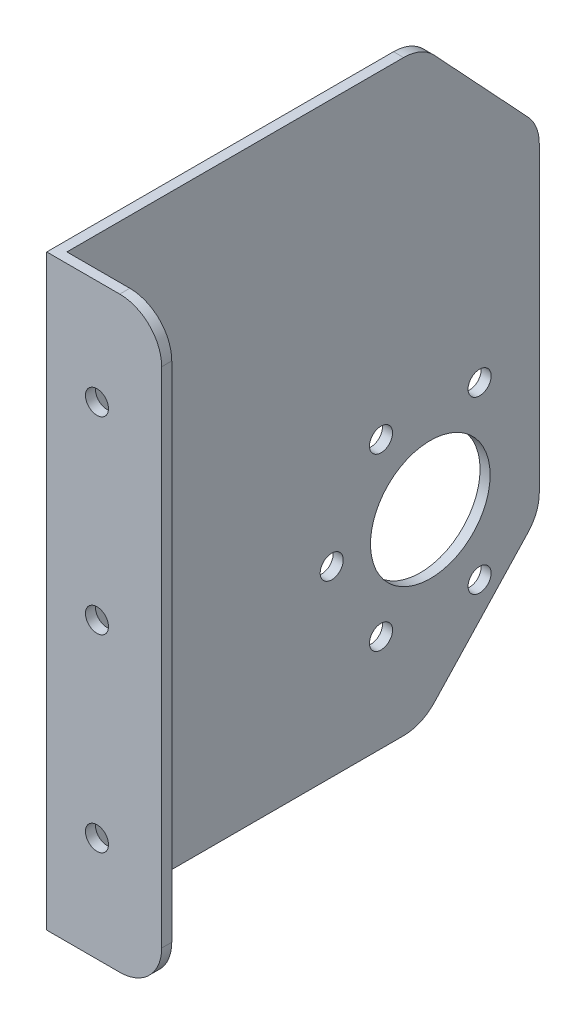
SolidWorks part; units mm, degrees
ref_plane "Front Plane" through (0, 0, 0) normal (0, 0, 1) x (1, 0, 0)
ref_plane "Top Plane" through (0, 0, 0) normal (0, 1, 0) x (1, 0, 0)
ref_plane "Right Plane" through (0, 0, 0) normal (1, 0, 0) x (0, 0, -1)
sketch "Sketch1" plane through (0, 0, 0) normal (1, 0, 0) x (0, 0, -1)
  line L1 (0, 0) -> (115, 0)
  line L2 (0, 0) -> (0, -140)
  line L3 (0, -140) -> (115, -140)
  line L4 (115, 0) -> (115, -140)
  dimension "D1" = 115
  dimension "D2" = 140
extrude "Boss-Extrude1" add sketch "Sketch1" along normal blind 2.4
sketch "Sketch2" plane through (2.4, 0, 0) normal (1, 0, 0) x (0, 0, -1)
  line L0 (87, 0) -> (115, -30)
  line L1 (115, 0) -> (0, 0) construction
  line L2 (115, -140) -> (115, 0) construction
  line L3 (115, -30) -> (142.6162, -32.5054)
  line L4 (142.6162, -32.5054) -> (142.6162, 14.8756)
  line L5 (142.6162, 14.8756) -> (87, 0)
  line L6 (115, -110) -> (87, -140)
  line L7 (0, -140) -> (115, -140) construction
  line L8 (87, -140) -> (87, -152.6611)
  line L9 (87, -152.6611) -> (136.31, -152.6611)
  line L10 (136.31, -152.6611) -> (115, -110)
  line L12 (0, 0) -> (0, -140) construction
  dimension "D1" = 30
  dimension "D2" = 87
  dimension "D3" = 87
  dimension "D4" = 30
extrude "Cut-Extrude1" cut sketch "Sketch2" against normal through all
fillet "Fillet1" radius 10 4 edges at (1.2, -140, -87) (1.2, -110, -115) (1.2, -30, -115) (1.2, 0, -87)
sketch "Sketch3" plane through (2.4, 0, 0) normal (1, 0, 0) x (0, 0, -1)
  line L0 (82.6545, 0) -> (0, 0) construction
  line L1 (0, -140) -> (2.4, -140)
  line L2 (0, -140) -> (0, 0)
  line L3 (0, 0) -> (2.4, 0)
  line L4 (2.4, -140) -> (2.4, 0)
  dimension "D1" = 2.4
extrude "Boss-Extrude2" add sketch "Sketch3" along normal blind 25
fillet "Fillet2" radius 10 2 edges at (27.4, -140, -1.2) (27.4, 0, -1.2)
sketch "Sketch4" plane through (0, 0, 0) normal (0, 0, 1) x (1, 0, 0)
  line L0 (17.4, 0) -> (0, 0) construction
  line L1 (17.4, -140) -> (0, -140) construction
  line L2 (27.4, -10) -> (27.4, -130) construction
  circle A0 centre (11.975, -70) radius 2.75
  circle A1 centre (11.975, -25) radius 2.75
  circle A2 centre (11.975, -115) radius 2.75
  point P12 (27.4, -70)
  dimension "D1" = 5.5
  dimension "D2" = 5.5
  dimension "D3" = 5.5
  dimension "D4" = 25
  dimension "D5" = 25
extrude "Cut-Extrude2" cut sketch "Sketch4" against normal through all
sketch "Sketch5" plane through (2.4, 0, 0) normal (1, 0, 0) x (0, 0, -1)
  circle A2 centre (89.0279, -96.494) radius 14.26 construction
  circle A13 centre (89.0279, -96.494) radius 14.26
  circle A14 centre (77.2779, -76.1424) radius 2.75 construction
  circle A15 centre (77.2779, -76.1424) radius 2.75
  circle A16 centre (100.7779, -76.1424) radius 2.75 construction
  circle A17 centre (100.7779, -76.1424) radius 2.75
  circle A20 centre (100.7779, -116.8456) radius 2.75 construction
  circle A21 centre (100.7779, -116.8456) radius 2.75
  circle A22 centre (77.2779, -116.8456) radius 2.75 construction
  circle A23 centre (77.2779, -116.8456) radius 2.75
  circle A24 centre (65.5279, -96.494) radius 2.75 construction
  circle A25 centre (65.5279, -96.494) radius 2.75
extrude "Cut-Extrude3" cut sketch "Sketch5" against normal through all
